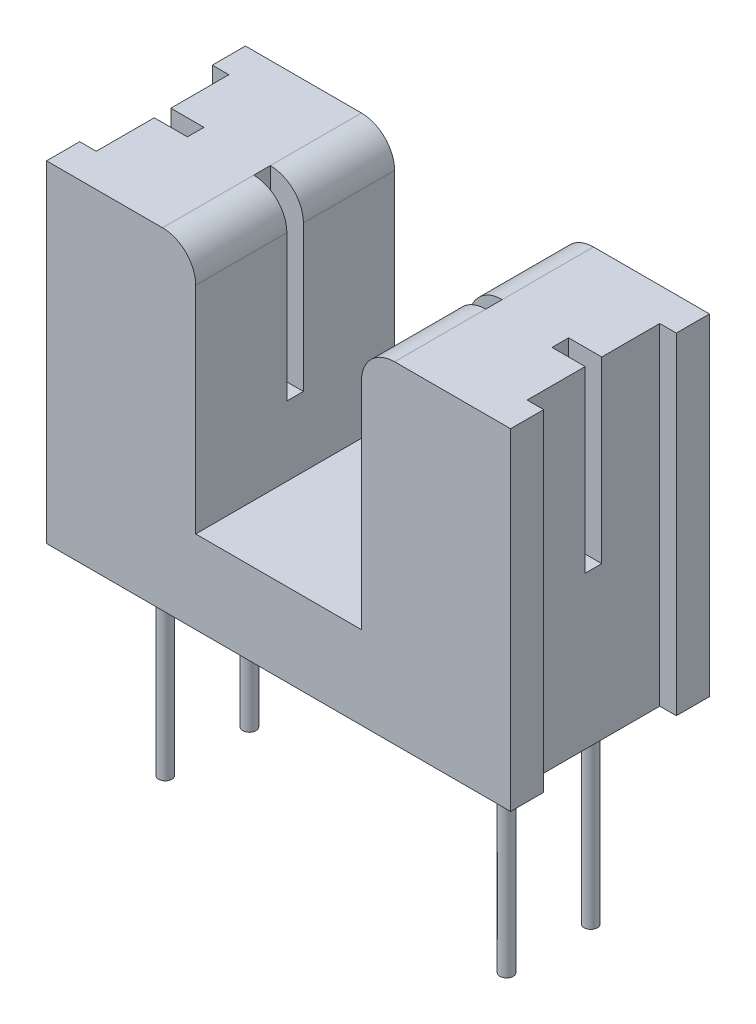
SolidWorks part; units mm, degrees
ref_plane "Front Plane" through (0, 0, 0) normal (0, 0, 1) x (1, 0, 0)
ref_plane "Top Plane" through (0, 0, 0) normal (0, 1, 0) x (1, 0, 0)
ref_plane "Right Plane" through (0, 0, 0) normal (1, 0, 0) x (0, 0, -1)
sketch "Sketch1" plane through (0, 0, 0) normal (0, 0, 1) x (1, 0, 0)
  line L0 (-7, -5) -> (-7, 5)
  line L1 (-7, 5) -> (-3.5, 5)
  line L2 (-2.5, 4) -> (-2.5, -2.5)
  line L3 (-2.5, -2.5) -> (2.5, -2.5)
  line L4 (2.5, -2.5) -> (2.5, 4)
  line L5 (3.5, 5) -> (7, 5)
  line L6 (7, 5) -> (7, -5)
  line L12 (-7, -5) -> (7, -5)
  line L13 (-7, 5) -> (7, -5) construction
  arc A0 (3.5, 5) -> (2.5, 4) centre (3.5, 4) ccw
  arc A1 (-2.5, 4) -> (-3.5, 5) centre (-3.5, 4) ccw
  point P12 (2.5, -2.2472)
  dimension "D1" = 1
  dimension "D2" = 5
  dimension "D3" = 14
  dimension "D4" = 2.5
  dimension "D5" = 10
extrude "Boss-Extrude1" add sketch "Sketch1" along normal mid plane 6
sketch "Sketch4" plane through (0, 5, 0) normal (0, 1, 0) x (1, 0, 0)
  line L0 (-7, -3) -> (-7, 3) construction
  line L1 (-7, 2) -> (-6.5, 2)
  line L2 (-7, 2) -> (-7, -2)
  line L3 (-7, -2) -> (-6.5, -2)
  line L4 (-6.5, 2) -> (-6.5, -2)
  line L5 (7, -3) -> (7, 3) construction
  line L6 (7, 2) -> (6.5, 2)
  line L7 (7, 2) -> (7, -2)
  line L8 (7, -2) -> (6.5, -2)
  line L9 (6.5, 2) -> (6.5, -2)
  line L10 (-3.5, 3) -> (-7, 3) construction
  point P12 (0, 0)
  point P13 (-6.5, 0)
  dimension "D1" = 1
  dimension "D2" = 0.5
extrude "Cut-Extrude2" cut sketch "Sketch4" against normal through all
sketch "Sketch2" plane through (0, 5, 0) normal (0, 1, 0) x (1, 0, 0)
  line L1 (-6.5, 0.25) -> (-5.5, 0.25)
  line L2 (-6.5, 0.25) -> (-6.5, -0.25)
  line L3 (-6.5, -0.25) -> (-5.5, -0.25)
  line L4 (-5.5, 0.25) -> (-5.5, -0.25)
  line L5 (-2.5, -3) -> (-2.5, 3) construction
  line L6 (-2.5, 0.25) -> (-3.5, 0.25)
  line L7 (-2.5, 0.25) -> (-2.5, -0.25)
  line L8 (-2.5, -0.25) -> (-3.5, -0.25)
  line L9 (-3.5, 0.25) -> (-3.5, -0.25)
  line L10 (2.5, -3) -> (2.5, 3) construction
  line L11 (2.5, 0.25) -> (3.5, 0.25)
  line L12 (2.5, 0.25) -> (2.5, -0.25)
  line L13 (2.5, -0.25) -> (3.5, -0.25)
  line L14 (3.5, 0.25) -> (3.5, -0.25)
  line L16 (6.5, 0.25) -> (5.5, 0.25)
  line L17 (6.5, 0.25) -> (6.5, -0.25)
  line L18 (6.5, -0.25) -> (5.5, -0.25)
  line L19 (5.5, 0.25) -> (5.5, -0.25)
  line L20 (-6.5, -2) -> (-6.5, 2) construction
  line L21 (6.5, 2) -> (6.5, -2) construction
  point P4 (0, 0)
  point P22 (0, 0)
  point P24 (0, 0)
  point P25 (-2.5, 0)
  dimension "D1" = 0.5
  dimension "D2" = 1
extrude "Cut-Extrude1" cut sketch "Sketch2" against normal blind 5.4
sketch "Sketch5" plane through (0, -5, 0) normal (0, -1, 0) x (1, 0, 0)
  line L0 (-6, 2.5) -> (-3.5, 2.5)
  line L1 (-3.5, 2.5) -> (-3.5, 1)
  line L2 (-3.5, 1) -> (-2.5, 1)
  line L3 (-2.5, 1) -> (-2.5, 2)
  line L4 (-2.5, 2) -> (2.5, 2)
  line L5 (2.5, 2) -> (2.5, 1)
  line L6 (2.5, 1) -> (3.5, 1)
  line L7 (3.5, 1) -> (3.5, 2.5)
  line L8 (3.5, 2.5) -> (6, 2.5)
  line L9 (6, 2.5) -> (6, -2.5)
  line L10 (6, -2.5) -> (3.5, -2.5)
  line L11 (3.5, -2.5) -> (3.5, -1)
  line L12 (3.5, -1) -> (2.5, -1)
  line L13 (2.5, -1) -> (2.5, -2)
  line L14 (2.5, -2) -> (-2.5, -2)
  line L15 (-2.5, -2) -> (-2.5, -1)
  line L16 (-2.5, -1) -> (-3.5, -1)
  line L17 (-3.5, -1) -> (-3.5, -2.5)
  line L18 (-3.5, -2.5) -> (-6, -2.5)
  line L19 (-6, -2.5) -> (-6, 2.5)
  line L20 (-7, 3) -> (7, 3) construction
  line L21 (-6.5, 2) -> (-6.5, -2) construction
  point P17 (-6, 0)
  point P21 (0, 2)
  point P23 (-3.7209, 2.507)
  point P24 (3.7497, -2.5501)
  point P25 (0, 0)
  point P30 (-3.1894, -2.1191)
  point P31 (-3.2325, -1.1421)
  point P32 (-2.7296, -1.1134)
  point P33 (3.0744, -1.8892)
  point P34 (3.8071, 2.5788)
  point P35 (3.7928, 2.5)
  dimension "D1" = 1
  dimension "D2" = 0.5
  dimension "D3" = 0.5
  dimension "D4" = 1
  dimension "D5" = 1
  dimension "D6" = 2.5
extrude "Cut-Extrude3" cut sketch "Sketch5" against normal blind 1.5
sketch "Sketch6" plane through (0, -3.5, 0) normal (0, -1, 0) x (1, 0, 0)
  line L1 (-6, -2.5) -> (-3.5, -2.5)
  line L2 (-6, -2.5) -> (-6, 2.5)
  line L3 (-6, 2.5) -> (-3.5, 2.5)
  line L4 (-3.5, -2.5) -> (-3.5, 2.5)
  line L5 (3.5, -2.5) -> (6, -2.5)
  line L6 (3.5, -2.5) -> (3.5, 2.5)
  line L7 (3.5, 2.5) -> (6, 2.5)
  line L8 (6, -2.5) -> (6, 2.5)
extrude "Cut-Extrude4" cut sketch "Sketch6" against normal offset from surface (3 mm away) 0.1 up to face at (-6, -0.4, 0)
sketch "Sketch7" plane through (0, -0.5, 0) normal (0, -1, 0) x (1, 0, 0)
  line L1 (5.15, -1.27) -> (-5.15, -1.27) construction
  line L2 (5.15, -1.27) -> (5.15, 1.27) construction
  line L3 (5.15, 1.27) -> (-5.15, 1.27) construction
  line L4 (-5.15, -1.27) -> (-5.15, 1.27) construction
  line L5 (5.15, -1.27) -> (-5.15, 1.27) construction
  line L6 (5.15, 1.27) -> (-5.15, -1.27) construction
  circle A0 centre (-5.15, -1.27) radius 0.2
  circle A1 centre (-5.15, 1.27) radius 0.2
  circle A2 centre (5.15, 1.27) radius 0.2
  circle A3 centre (5.15, -1.27) radius 0.2
  point P0 (0, 0)
  dimension "D3" = 0.4
  dimension "D1" = 2.54
  dimension "D2" = 10.3
extrude "Boss-Extrude2" add sketch "Sketch7" along normal offset from surface (10.5 mm away) 6 up to face at (0, -5, 0) offset beyond the face yes
ref_plane "Plane1" through (0, 2.5, 0) normal (0, -1, 0) x (-1, 0, 0)
ref_axis "Axis1" through (-7.7, 2.5, 0) along (1, 0, 0)
